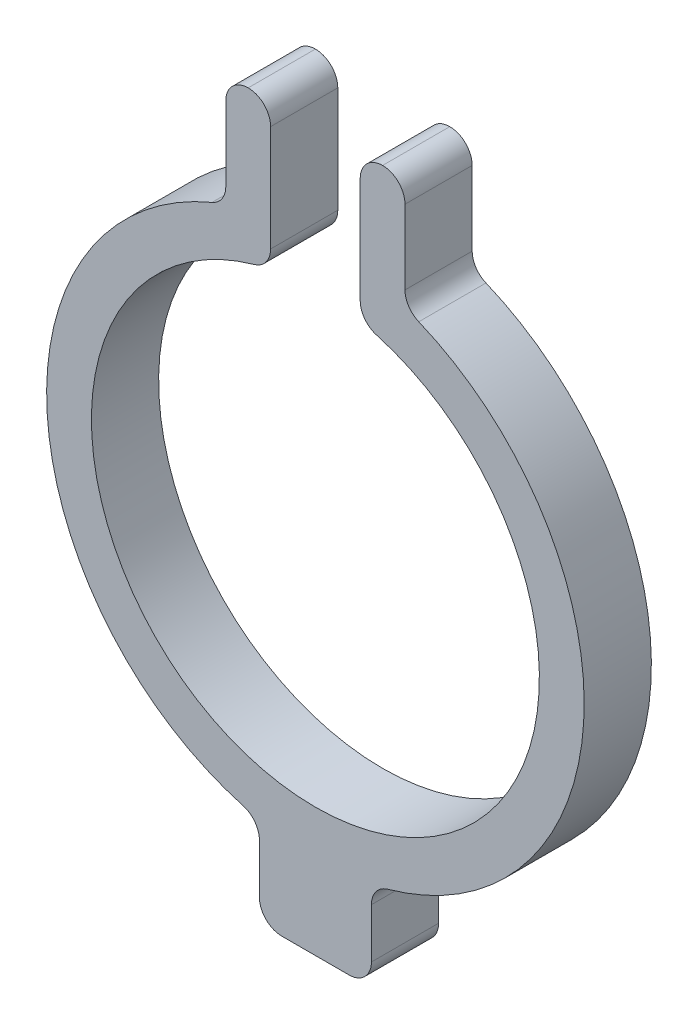
SolidWorks part; units mm, degrees
ref_plane "Front Plane" through (0, 0, 0) normal (0, 0, 1) x (1, 0, 0)
ref_plane "Top Plane" through (0, 0, 0) normal (0, 1, 0) x (1, 0, 0)
ref_plane "Right Plane" through (0, 0, 0) normal (1, 0, 0) x (0, 0, -1)
sketch "Sketch1" plane through (0, 0, 0) normal (0, 0, 1) x (1, 0, 0)
  line L0 (4, 32.6274) -> (8, 32.6274)
  line L4 (4, 19.5959) -> (4, 32.6274)
  line L6 (-5, -23.4734) -> (-5, -31.4734)
  line L8 (-8, 22.6274) -> (-8, 32.6274)
  line L9 (-8, 32.6274) -> (-4, 32.6274)
  line L10 (8, 22.6274) -> (8, 32.6274)
  line L11 (5, -23.4734) -> (5, -31.4734)
  line L13 (-5, -31.4734) -> (5, -31.4734)
  line L14 (0, 0) -> (0, -12.6215) construction
  line L16 (-4, 19.5959) -> (-4, 32.6274)
  arc A0 (-4, 19.5959) -> (4, 19.5959) centre (0, 0) ccw
  arc A3 (-8, 22.6274) -> (-5, -23.4734) centre (0, 0) ccw
  arc A4 (5, -23.4734) -> (8, 22.6274) centre (0, 0) ccw
  point P3 (0, 20)
  point P9 (0.4388, 23.8641)
  dimension "D1" = 40
  dimension "D4" = 24
  dimension "D2" = 10
  dimension "D3" = 8
  dimension "D5" = 8
  dimension "D6" = 4
  dimension "D7" = 4
  dimension "D8" = 10
extrude "Boss-Extrude1" add sketch "Sketch1" along normal blind 6 contours L8 A3 L10 L0 L4 A0 L16 L9 region at (6, 31.8266, 0)
fillet "Fillet1" radius 2 12 edges at (-4, 19.5959, 3) (4, 19.5959, 3) (-8, 22.6274, 3) (8, 32.6274, 3) (4, 32.6274, 3) (-4, 32.6274, 3) (-8, 32.6274, 3) (-5, -31.4734, 3) (-5, -23.4734, 3) (5, -31.4734, 3) (5, -23.4734, 3) (8, 22.6274, 3)
